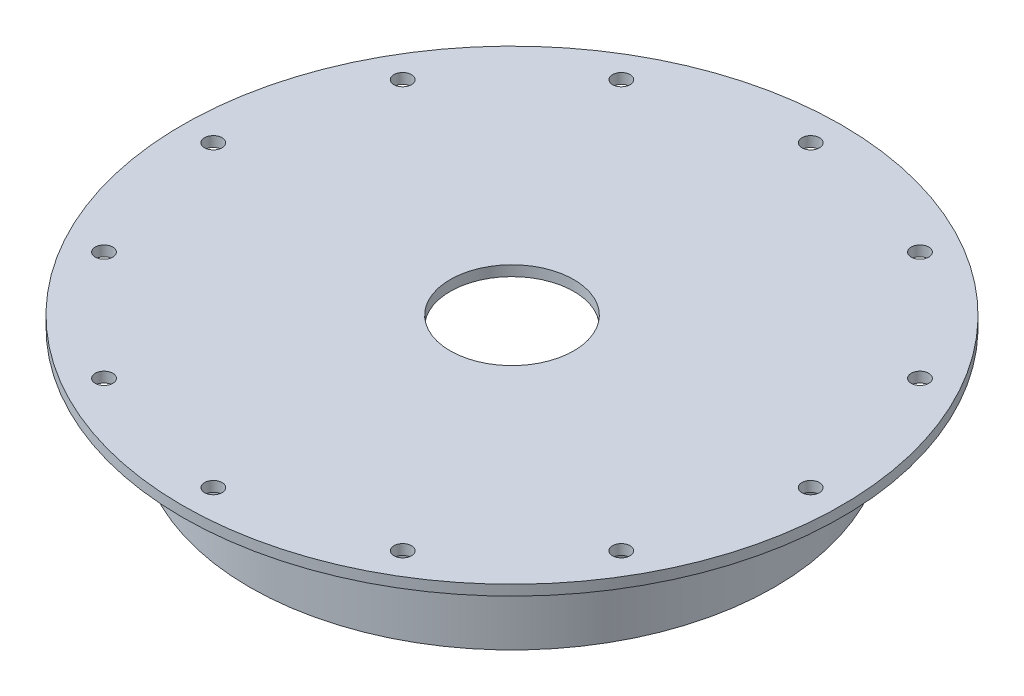
SolidWorks part; units mm, degrees
material "6063-T6"
ref_plane "Front Plane" through (0, 0, 0) normal (0, 0, 1) x (1, 0, 0)
ref_plane "Top Plane" through (0, 0, 0) normal (0, 1, 0) x (1, 0, 0)
ref_plane "Right Plane" through (0, 0, 0) normal (1, 0, 0) x (0, 0, -1)
ref_axis "Axis1" through (0, 55, 0) along (0, -1, 0)
sketch "Sketch1" plane through (0, 0, 0) normal (0, 0, 1) x (1, 0, 0)
  line L0 (-50.8, 0) -> (-40.4361, 0)
  line L1 (0, 55) -> (0, -55) construction
  line L2 (-50.8, 0) -> (-50.8, 1.5875)
  line L3 (-50.8, 1.5875) -> (-9.525, 1.5875)
  line L4 (-50.8, 1.5875) -> (-9.525, 1.5875) construction
  line L5 (-9.525, 1.5875) -> (-9.525, 0)
  line L6 (-9.525, 0) -> (0, 0) construction
  line L7 (-50.8, 0) -> (-50.8, 1.5875) construction
  line L8 (-9.525, 1.5875) -> (-9.525, 0) construction
  line L9 (-40.4361, 0) -> (-40.4361, -14.5167)
  line L10 (-40.4361, -14.5167) -> (-35.3309, -14.5167)
  line L11 (-35.3309, -14.5167) -> (-35.3309, 0)
  line L12 (-35.3309, 0) -> (-9.525, 0)
revolve "Revolve1" add sketch "Sketch1" angle 360 about axis through (0, 55, 0) along (0, -1, 0)
ref_plane "Hole Location Plane" through (0, 3.175, 0) normal (0, 1, 0) x (1, 0, 0)
sketch "Hole Location" plane through (0, 3.175, 0) normal (0, 1, 0) x (1, 0, 0)
  line L0 (0, 0) -> (-46.0375, 0) construction
  circle A0 centre (0, 0) radius 46.0375 construction
  dimension "D1" = 92.075
hole_wizard "#36 (0.1065) Diameter Hole1" positions "Sketch4" profile "Sketch5" hole size "#36" standard "ANSI Inch" end condition through all
sketch "Sketch4" plane through (0, 1.5875, 0) normal (0, 1, 0) x (1, 0, 0)
  point P0 (-46.0375, 0)
sketch "Sketch5" plane through (-46.0375, 1.5875, 0) normal (1, 0, 0) x (0, 0, 1)
  line L0 (0, 0) -> (0, 16.1042)
  line L1 (0, 16.1042) -> (1.3525, 16.1042)
  line L2 (1.3525, 16.1042) -> (1.3525, 0)
  line L5 (1.3525, 0) -> (0, 0)
  line L11 (0, -6.35) -> (0, 107.95) construction
  dimension "Thru Hole Dia." = 2.7051
  dimension "Thru Hole Depth" = 16.1042
pattern_circular "CirPattern1" count 12 every 30 about axis through (0, 55, 0) along (0, -1, 0) of "#36 (0.1065) Diameter Hole1"
equation "\"D1@Hole Location\"=\"TANK DIAMETER@Cryo Tank.Assembly\"+\"GASKET SEAT THICKNESS@Cryo Tank.Assembly\"+\"LINER THICKNESS@Cryo Tank.Assembly\""
